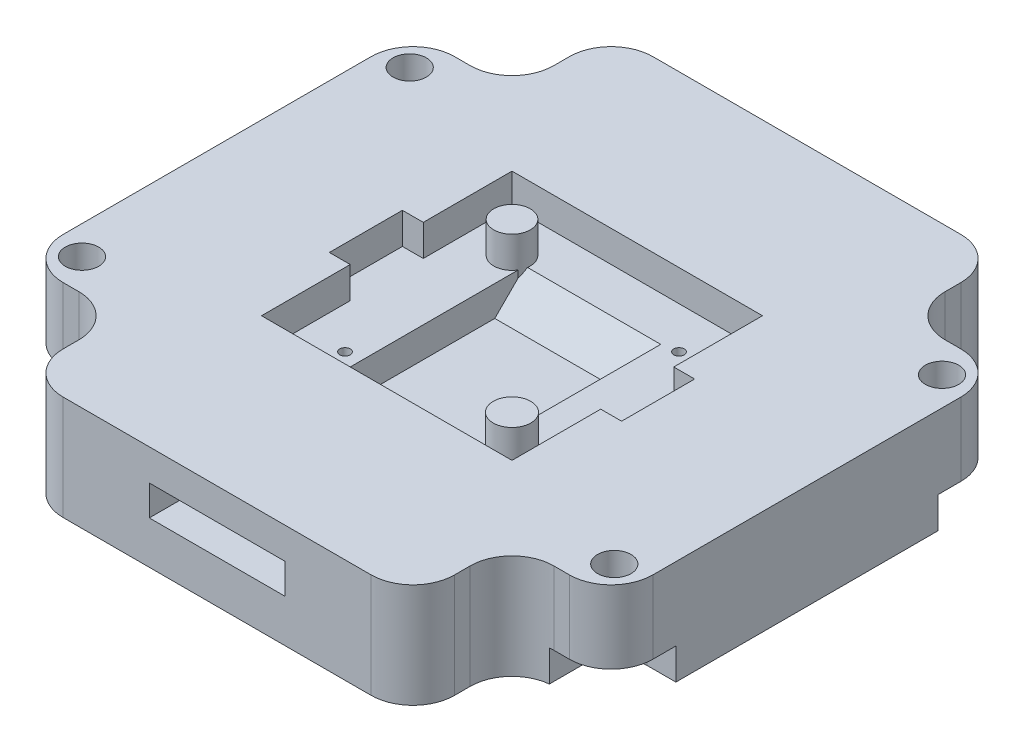
SolidWorks part; units mm, degrees
ref_plane "Ebene vorne" through (0, 0, 0) normal (0, 0, 1) x (1, 0, 0)
ref_plane "Ebene oben" through (0, 0, 0) normal (0, 1, 0) x (1, 0, 0)
ref_plane "Ebene rechts" through (0, 0, 0) normal (1, 0, 0) x (0, 0, -1)
sketch "Skizze1" plane through (0, 0, 0) normal (0, 1, 0) x (1, 0, 0)
  line L0 (18.75, 18.75) -> (28.25, 18.75)
  line L1 (-28.25, 18.75) -> (-18.75, 18.75)
  line L2 (-28.25, 18.75) -> (-28.25, -18.75)
  line L3 (-28.25, -18.75) -> (-18.75, -18.75)
  line L4 (28.25, 18.75) -> (28.25, -18.75)
  line L5 (-28.25, 18.75) -> (28.25, -18.75) construction
  line L6 (-28.25, -18.75) -> (28.25, 18.75) construction
  line L7 (-18.75, -28.25) -> (18.75, -28.25)
  line L8 (-18.75, -28.25) -> (-18.75, -18.75)
  line L9 (-18.75, 28.25) -> (18.75, 28.25)
  line L10 (18.75, -28.25) -> (18.75, -18.75)
  line L11 (-18.75, -28.25) -> (18.75, 28.25) construction
  line L12 (-18.75, 28.25) -> (18.75, -28.25) construction
  line L13 (18.75, 18.75) -> (18.75, 28.25)
  line L14 (18.75, -18.75) -> (28.25, -18.75)
  line L15 (-18.75, 18.75) -> (-18.75, 28.25)
  point P0 (0, 0)
  point P6 (0, 0)
  dimension "D1" = 56.5
  dimension "D2" = 56.5
  dimension "D3" = 37.5
extrude "Aufsatz-Linear austragen1" add sketch "Skizze1" along normal blind 10
sketch "Skizze2" plane through (0, 10, 0) normal (0, 1, 0) x (1, 0, 0)
  line L1 (-12, 12) -> (12, 12)
  line L2 (-12, 12) -> (-12, -12)
  line L3 (-12, -12) -> (12, -12)
  line L4 (12, 12) -> (12, -12)
  line L5 (-12, 12) -> (12, -12) construction
  line L6 (-12, -12) -> (12, 12) construction
  point P0 (0, 0)
  dimension "D1" = 24
extrude "Schnitt-Linear austragen1" cut sketch "Skizze2" against normal blind 3
fillet "Verrundung1" radius 4 12 edges at (-28.25, 5, 18.75) (-18.75, 5, 28.25) (-28.25, 5, -18.75) (-18.75, 5, -28.25) (18.75, 5, -28.25) (28.25, 5, -18.75) (28.25, 5, 18.75) (18.75, 5, 28.25) (18.75, 5, 18.75) (-18.75, 5, 18.75) (-18.75, 5, -18.75) (18.75, 5, -18.75)
sketch "Skizze3" plane through (0, 7, 0) normal (0, 1, 0) x (1, 0, 0)
  line L1 (-8, -8) -> (8, -8) construction
  line L2 (-8, -8) -> (-8, 8) construction
  line L3 (-8, 8) -> (8, 8) construction
  line L4 (8, -8) -> (8, 8) construction
  line L5 (-8, -8) -> (8, 8) construction
  line L6 (-8, 8) -> (8, -8) construction
  circle A0 centre (-8, 8) radius 1.75
  circle A2 centre (8, -8) radius 1.8
  point P0 (0, 0)
  dimension "D2" = 3.5
  dimension "D1" = 16
extrude "Aufsatz-Linear austragen2" add sketch "Skizze3" along normal blind 3
sketch "Skizze4" plane through (0, 10, 0) normal (0, 1, 0) x (1, 0, 0)
  line L0 (0, 0) -> (-50000, 0) construction
  line L1 (12, 3.5) -> (14, 3.5)
  line L2 (12, -12) -> (12, 12) construction
  line L3 (14, 3.5) -> (14, -3.5)
  line L4 (14, -3.5) -> (12, -3.5)
  line L5 (12, -3.5) -> (12, 3.5)
  dimension "D1" = 2
  dimension "D2" = 7
extrude "Schnitt-Linear austragen2" cut sketch "Skizze4" against normal blind 3
mirror "Spiegeln1" about plane through (0, 0, 0) normal (1, 0, 0) of "Schnitt-Linear austragen2"
sketch "Skizze5" plane through (0, 0, 28.25) normal (0, 0, 1) x (1, 0, 0)
  line L0 (0, 0) -> (0, -50000) construction
  line L2 (-14.75, 0) -> (14.75, 0) construction
  line L3 (-6.5, 7) -> (6.5, 7)
  line L4 (-6.5, 7) -> (-6.5, 4.1)
  line L5 (-6.5, 4.1) -> (6.5, 4.1)
  line L6 (6.5, 7) -> (6.5, 4.1)
  line L7 (-6.5, 7) -> (6.5, 4.1) construction
  line L8 (-6.5, 4.1) -> (6.5, 7) construction
  point P3 (0, 5.55)
  dimension "D1" = 2.9
  dimension "D2" = 13
  dimension "D3" = 4.1
extrude "Schnitt-Linear austragen3" cut sketch "Skizze5" against normal blind 32
chamfer "Fase1" distance 4 angle 45 1 edges at (0, 7, -3.75)
hole_wizard "Ø3.2 (3.2) Durchmesser Bohrung1" positions "Skizze8" profile "Skizze9" hole size "Ø3.2" standard "ISO"
sketch "Skizze8" plane through (0, 10, 0) normal (0, 1, 0) x (1, 0, 0)
  line L1 (25.5, 15.7) -> (-25.5, 15.7) construction
  line L2 (25.5, 15.7) -> (25.5, -15.7) construction
  line L3 (25.5, -15.7) -> (-25.5, -15.7) construction
  line L4 (-25.5, 15.7) -> (-25.5, -15.7) construction
  line L5 (25.5, 15.7) -> (-25.5, -15.7) construction
  line L6 (25.5, -15.7) -> (-25.5, 15.7) construction
  point P2 (-25.5, -15.7)
  point P195 (25.5, 15.7)
  point P196 (25.5, -15.7)
  point P197 (-25.5, 15.7)
  dimension "D1" = 51
  dimension "D2" = 31.4
sketch "Skizze9" plane through (-25.5, 10, 15.7) normal (1, 0, 0) x (0, 0, 1)
  line L0 (0, 0) -> (0, 11.9614)
  line L1 (0, 11.9614) -> (1.6, 11)
  line L2 (1.6, 11) -> (1.6, 0)
  line L5 (1.6, 0) -> (0, 0)
  line L10 (0, 11.9614) -> (-1.6, 11) construction
  line L11 (0, -6.35) -> (0, 107.95) construction
  dimension "Bohrerdurchmesser" = 3.2
  dimension "Bohrungstiefe" = 11
  dimension "Spitzenwinkel" = 118
hole_wizard "Ø1.0 (1) Durchmesser Bohrung1" positions "Skizze10" profile "Skizze11" hole size "Ø1.0" standard "ISO"
sketch "Skizze10" plane through (0, 7, 0) normal (0, 1, 0) x (1, 0, 0)
  line L1 (-8, 8) -> (8, 8)
  line L2 (-8, 8) -> (-8, -8)
  line L3 (-8, -8) -> (8, -8)
  line L4 (8, 8) -> (8, -8)
  line L5 (-8, 8) -> (8, -8) construction
  line L6 (-8, -8) -> (8, 8) construction
  point P456 (-8, -8)
  point P457 (8, 8)
  point P466 (0, 0)
sketch "Skizze11" plane through (8, 7, -8) normal (1, 0, 0) x (0, 0, 1)
  line L0 (0, 0) -> (0, 5.3004)
  line L1 (0, 5.3004) -> (0.5, 5)
  line L2 (0.5, 5) -> (0.5, 0)
  line L5 (0.5, 0) -> (0, 0)
  line L10 (0, 5.3004) -> (-0.5, 5) construction
  line L11 (0, -6.35) -> (0, 107.95) construction
  dimension "Bohrerdurchmesser" = 1
  dimension "Bohrungstiefe" = 5
  dimension "Spitzenwinkel" = 118
sketch "Skizze12" plane through (0, 0, 0) normal (0, -1, 0) x (1, 0, 0)
  line L0 (-22.35, 15.7) -> (-22.35, 18.85)
  line L1 (-25.5, 18.85) -> (-22.35, 18.85)
  line L2 (-25.5, 12.55) -> (-28.65, 12.55)
  line L3 (-28.65, 12.55) -> (-28.65, 15.7)
  arc A0 (-25.5, 12.55) -> (-22.35, 15.7) centre (-25.5, 15.7) ccw
  arc A1 (-25.5, 18.85) -> (-28.65, 15.7) centre (-25.5, 15.7) ccw
  dimension "D1" = 6.3
extrude "Schnitt-Linear austragen4" cut sketch "Skizze12" against normal blind 3
mirror "Spiegeln2" about plane through (0, 0, 0) normal (1, 0, 0) of "Schnitt-Linear austragen4"
mirror "Spiegeln3" about plane through (0, 0, 0) normal (0, 0, 1) of "Spiegeln2"
